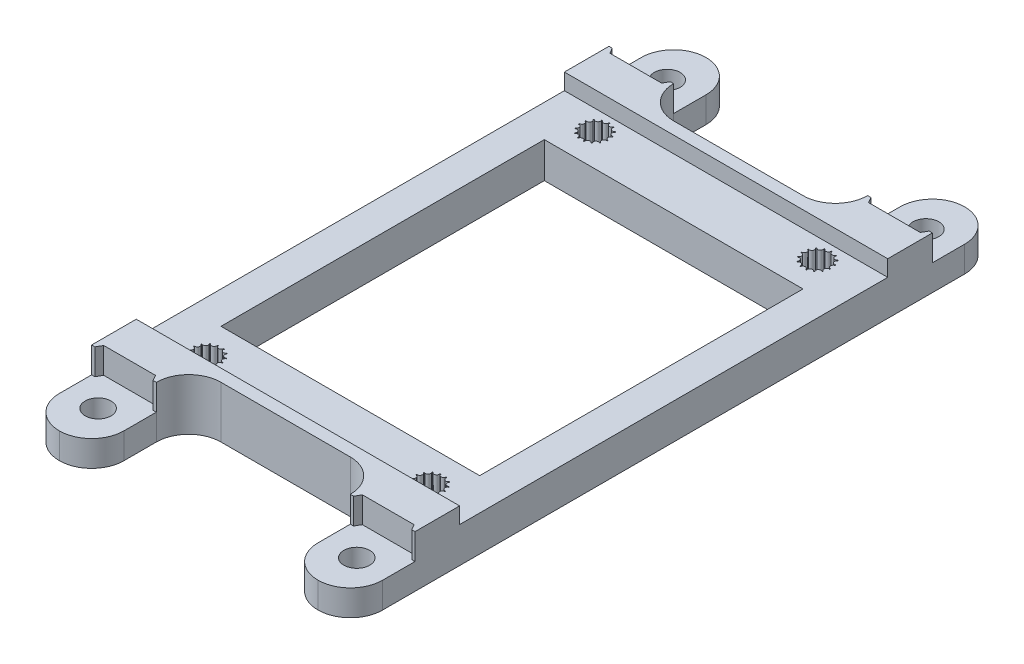
SolidWorks part; units mm, degrees
ref_plane "Front Plane" through (0, 0, 0) normal (0, 0, 1) x (1, 0, 0)
ref_plane "Top Plane" through (0, 0, 0) normal (0, 1, 0) x (1, 0, 0)
ref_plane "Right Plane" through (0, 0, 0) normal (1, 0, 0) x (0, 0, -1)
sketch "Sketch1" plane through (0, 0, 0) normal (0, 1, 0) x (1, 0, 0)
  line L1 (0, 0) -> (50, 0)
  line L2 (0, 0) -> (0, 70)
  line L3 (0, 70) -> (50, 70)
  line L4 (50, 0) -> (50, 70)
  dimension "D1" = 50
  dimension "D2" = 70
extrude "Boss-Extrude1" add sketch "Sketch1" along normal blind 8
sketch "Sketch2" plane through (0, 8, 0) normal (0, 1, 0) x (1, 0, 0)
  line L4 (0, 70) -> (0, 0)
  line L5 (0, 0) -> (50, 0)
  line L6 (50, 0) -> (50, 70)
  line L7 (50, 70) -> (0, 70)
  line L8 (0, 70) -> (0, 0)
  line L9 (0, 0) -> (50, 0)
  line L10 (50, 0) -> (50, 70)
  line L11 (50, 70) -> (0, 70)
  circle A0 centre (7.8, 5) radius 2.25
  circle A1 centre (7.8, 7.25) radius 0.4
  circle A2 centre (8.7152, 7.0555) radius 0.4
  circle A3 centre (9.4721, 6.5055) radius 0.4
  circle A4 centre (9.9399, 5.6953) radius 0.4
  circle A5 centre (10.0377, 4.7648) radius 0.4
  circle A6 centre (9.7486, 3.875) radius 0.4
  circle A7 centre (9.1225, 3.1797) radius 0.4
  circle A8 centre (8.2678, 2.7992) radius 0.4
  circle A9 centre (7.3322, 2.7992) radius 0.4
  circle A10 centre (6.4775, 3.1797) radius 0.4
  circle A11 centre (5.8514, 3.875) radius 0.4
  circle A12 centre (5.5623, 4.7648) radius 0.4
  circle A13 centre (5.6601, 5.6953) radius 0.4
  circle A14 centre (6.1279, 6.5055) radius 0.4
  circle A15 centre (6.8848, 7.0555) radius 0.4
  point P38 (7.8, 5)
  dimension "D4" = 4.5
  dimension "D5" = 0.8
  dimension "D2" = 5
  dimension "D3" = 7.8
  dimension "D1" = 0
  dimension "D6" = 15
extrude "Cut-Extrude1" cut sketch "Sketch2" against normal blind 8 contours A15 A0 A14 A13 A12 A11 A10 A9 A8 A7 A6 A5 A4 A3 A2 A1
ref_plane "Plane1" through (25, 0, 0) normal (-1, 0, 0) x (0, 0, 1)
ref_plane "Plane2" through (0, 0, -35) normal (0, 0, -1) x (-1, 0, 0)
mirror "Mirror1" about plane through (0, 0, -35) normal (0, 0, -1) of "Cut-Extrude1" second plane through (25, 0, 0) second plane normal (-1, 0, 0)
sketch "Sketch3" plane through (0, 8, 0) normal (0, 1, 0) x (1, 0, 0)
  line L1 (0, 0) -> (10, 0)
  line L2 (0, 0) -> (0, -15)
  line L3 (0, -15) -> (10, -15)
  line L4 (10, 0) -> (10, -15)
  circle A0 centre (5, -9) radius 2
  dimension "D3" = 4
  dimension "D1" = 15
  dimension "D2" = 10
  dimension "D4" = 5
  dimension "D5" = 9
extrude "Boss-Extrude2" add sketch "Sketch3" against normal blind 8
mirror "Mirror2" about plane through (0, 0, -35) normal (0, 0, -1) of "Boss-Extrude2" second plane through (25, 0, 0) second plane normal (-1, 0, 0)
fillet "Fillet1" radius 5 20 edges at (0, 4, 15) (10, 4, 0) (5, 0, 15) (10, 4, 15) (5, 8, 15) (45, 0, 15) (45, 8, 15) (50, 4, 15) (40, 4, 15) (40, 4, 0) (5, 0, -85) (5, 8, -85) (0, 4, -85) (10, 4, -85) (10, 4, -70) (50, 4, -85) (40, 4, -70) (45, 0, -85) (40, 4, -85) (45, 8, -85)
sketch "Sketch4" plane through (0, 8, 0) normal (0, 1, 0) x (1, 0, 0)
  line L0 (0.5, -5) -> (0, -5)
  line L1 (0, -5) -> (0.5, -5)
  line L2 (9.5, -5) -> (15, -5)
  line L3 (15, -5) -> (15, -18.6205)
  line L4 (15, -18.6205) -> (0, -18.6205)
  line L5 (0, -18.6205) -> (0, -5)
  line L6 (0.5, -5) -> (1, -4.134)
  line L7 (1, -4.134) -> (9, -4.134)
  line L8 (5, -5) -> (5, -3.4503) construction
  line L9 (9.5, -5) -> (9, -4.134)
  arc A0 (9.5, -5) -> (0.5, -5) centre (5, -5) ccw
  point P11 (5, -4.134)
  dimension "D1" = 9
  dimension "D2" = 4
  dimension "D3" = 1
extrude "Cut-Extrude2" cut sketch "Sketch4" against normal blind 4 contours L2 A0 L0 L5 L4 L3
mirror "Mirror4" about plane through (0, 0, -35) normal (0, 0, -1) of "Cut-Extrude2" second plane through (25, 0, 0) second plane normal (-1, 0, 0)
sketch "Sketch5" plane through (0, 8, 0) normal (0, 1, 0) x (1, 0, 0)
  line L0 (4.4, 35) -> (-4.4, 35) construction
  line L1 (5, 60) -> (45, 60)
  line L2 (5, 60) -> (5, 10)
  line L3 (5, 10) -> (45, 10)
  line L4 (45, 60) -> (45, 10)
  line L5 (5, 60) -> (45, 10) construction
  line L6 (5, 10) -> (45, 60) construction
  line L7 (25, 4.4) -> (25, -4.4) construction
  line L8 (50, -5) -> (50, 75) construction
  line L9 (35, 70) -> (15, 70) construction
  point P0 (25, 35)
  dimension "D1" = 5
  dimension "D2" = 10
extrude "Cut-Extrude3" cut sketch "Sketch5" against normal blind 13
sketch "Sketch6" plane through (0, 8, 0) normal (0, 1, 0) x (1, 0, 0)
  line L0 (4.4, 35) -> (-4.4, 35) construction
  line L1 (0, 1.9) -> (50, 1.9)
  line L2 (0, 1.9) -> (0, 68.1)
  line L3 (0, 68.1) -> (50, 68.1)
  line L4 (50, 1.9) -> (50, 68.1)
  line L5 (0, 1.9) -> (50, 68.1) construction
  line L6 (0, 68.1) -> (50, 1.9) construction
  line L7 (25, 73.5713) -> (25, 35) construction
  line L8 (25, 4.4) -> (25, -4.4) construction
  line L9 (25, 35) -> (31.28, 35) construction
  line L10 (31.28, 35) -> (23.1876, 35) construction
  point P0 (25, 35)
  dimension "D1" = 66.2
  dimension "D2" = 50
extrude "Cut-Extrude4" cut sketch "Sketch6" against normal blind 2.5 contours L1 L4 L3 L2
sketch "Sketch7" plane through (0, 5.5, 0) normal (0, 1, 0) x (1, 0, 0)
  line L0 (25, 35) -> (25, 22.5954) construction
  line L1 (4.4, 35) -> (-4.4, 35) construction
  line L2 (25, 4.4) -> (25, -4.4) construction
  line L3 (25, 22.5954) -> (25, 35) construction
  line L4 (25, 35) -> (22.9274, 35) construction
  line L6 (41, 56) -> (9, 56)
  line L7 (41, 56) -> (41, 14)
  line L8 (41, 14) -> (9, 14)
  line L9 (9, 56) -> (9, 14)
  line L10 (41, 56) -> (9, 14) construction
  line L11 (41, 14) -> (9, 56) construction
  dimension "D1" = 32
  dimension "D2" = 42
